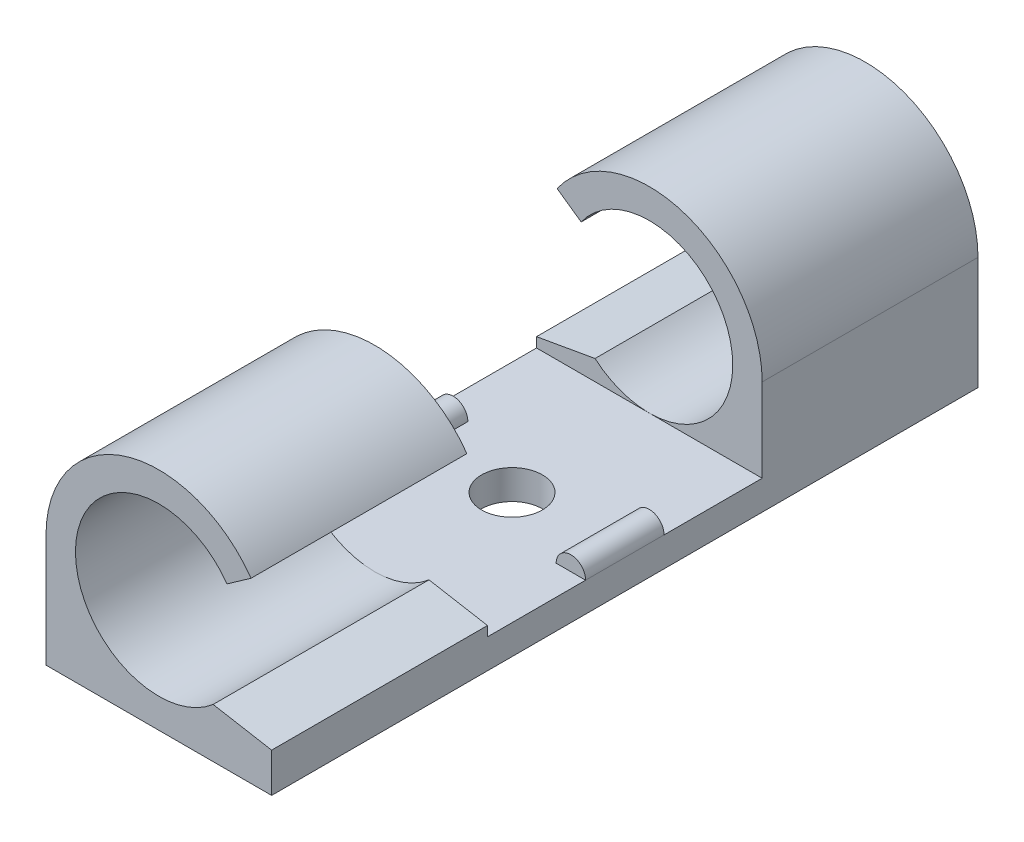
SolidWorks part; units mm, degrees
ref_plane "Plano frontal" through (0, 0, 0) normal (0, 0, 1) x (1, 0, 0)
ref_plane "Plano superior" through (0, 0, 0) normal (0, 1, 0) x (1, 0, 0)
ref_plane "Plano direito" through (0, 0, 0) normal (1, 0, 0) x (0, 0, -1)
sketch "Esboço1" plane through (0, 0, 0) normal (0, 0, 1) x (1, 0, 0)
  line L0 (-5.75, 0) -> (5.75, 0)
  line L1 (-5.75, 5.75) -> (5.75, 5.75)
  line L2 (-5.75, 5.75) -> (-5.75, -5.75)
  line L3 (-5.75, -5.75) -> (5.75, -5.75)
  line L4 (5.75, 5.75) -> (5.75, -5.75)
  line L5 (-5.75, 5.75) -> (5.75, -5.75) construction
  line L6 (-5.75, -5.75) -> (5.75, 5.75) construction
  circle A0 centre (0, 0) radius 5.75
  circle A2 centre (0, 0) radius 4.25
  point P0 (0, 0)
  point P12 (0, 0)
  dimension "D3" = 8.5
  dimension "D1" = 11.5
  dimension "D2" = 11.5
extrude "Ressalto-extrusão1" add sketch "Esboço1" along normal blind 11 contours A0 L2 L3 | A0 L3 L4 | A2 L0 A0 | A2 L0 A0 region at (0, 4.3786, 0) region at (5, -0.1286, 0) region at (4.4656, -4.4656, 0) region at (-4.4656, -4.4656, 0)
sketch "Esboço2" plane through (0, 0, 11) normal (0, 0, 1) x (1, 0, 0)
  line L0 (5.75, 0) -> (5.75, -5.75) construction
  line L1 (-5.75, -5.75) -> (5.75, -5.75)
  line L2 (-5.75, -5.75) -> (-5.75, -4.25)
  line L3 (-5.75, -4.25) -> (5.75, -4.25)
  line L4 (5.75, -5.75) -> (5.75, -4.25)
  line L5 (-5.75, -5.75) -> (5.75, -4.25) construction
  line L6 (-5.75, -4.25) -> (5.75, -5.75) construction
  circle A0 centre (0, 0) radius 4.25 construction
  point P4 (0, -5)
extrude "Ressalto-extrusão2" add sketch "Esboço2" along normal blind 7
sketch "Esboço3" plane through (0, 0, 18) normal (0, 0, 1) x (1, 0, 0)
  line L0 (5.75, -4.25) -> (0, -4.25) construction
  line L1 (5.75, -4.25) -> (0, -4.25) construction
  line L2 (0, 0) -> (0, -0.723) construction
  arc A0 (5.75, -4.25) -> (4.25, -4.25) centre (5, -4.25) ccw
  arc A1 (4.25, -4.25) -> (5.75, -4.25) centre (5, -4.25) ccw construction
  arc A2 (-5.75, -4.25) -> (-4.25, -4.25) centre (-5, -4.25) cw
  line M5 (5.75, -4.25) -> (-5.75, -4.25)
  dimension "D1" = 1.5
extrude "Ressalto-extrusão3" add sketch "Esboço3" against normal blind 2 contours A0 M5 | A2 M5 region at (5, -3.9317, 18) region at (-5, -3.9317, 18)
mirror "Espelhar1" about plane through (0, 0, 18) normal (0, 0, -1) of "Ressalto-extrusão2", "Ressalto-extrusão1", "Ressalto-extrusão3"
sketch "Esboço4" plane through (0, -4.25, 0) normal (0, 1, 0) x (1, 0, 0)
  line L0 (0, -11) -> (0, -18) construction
  line L2 (-4.25, -18) -> (4.25, -18) construction
  line L3 (-4.25, -16) -> (-4.25, -20) construction
  line L4 (4.25, -16) -> (4.25, -20) construction
  line L5 (-5.75, -11) -> (5.75, -11) construction
  circle A0 centre (0, -18) radius 1.55
  point P2 (0, 0)
  point P13 (0, -17.7766)
  dimension "D1" = 3.1
extrude "Corte-extrusão1" cut sketch "Esboço4" against normal blind 2
sketch "Esboço5" plane through (0, 0, 36) normal (0, 0, 1) x (1, 0, 0)
  line L0 (5.75, -3.75) -> (2, -3.75) construction
  line L1 (5.75, 0) -> (5.75, -5.75) construction
  line L2 (-5.75, -5.75) -> (5.75, -5.75) construction
  line L3 (5.2915, 2.25) -> (3.1939, 2.25) construction
  line L4 (3.1939, 2.25) -> (4.7007, 3.3115)
  line L5 (0, 0) -> (3.1939, 2.25) construction
  line L6 (5.75, -3.75) -> (2.7688, -3.2243)
  circle A0 centre (0, 0) radius 4.25 construction
  arc A1 (5.75, 0) -> (-5.75, 0) centre (0, 0) ccw construction
  circle M4 centre (0, 0) radius 4.25
  line M6 (5.75, -5.75) -> (5.75, 0)
  arc M7 (5.75, 0) -> (-5.75, 0) centre (0, 0) ccw
  dimension "D1" = 2
  dimension "D2" = 6
  dimension "D3" = 35.164
  dimension "D4" = 10
extrude "Corte-extrusão2" cut sketch "Esboço5" against normal blind 12 contours L4 L0 M4 M6 M7 region at (4.729, -0.6115, 36)
sketch "Esboço6" plane through (0, 0, 0) normal (0, 0, -1) x (-1, 0, 0)
  line L0 (5.75, -3.75) -> (2, -3.75) construction
  line L1 (5.75, 0) -> (5.75, -5.75) construction
  line L2 (5.75, -5.75) -> (-5.75, -5.75) construction
  line L3 (5.2031, 2.4474) -> (3.4746, 2.4474) construction
  line L4 (5.75, -3.75) -> (2.7688, -3.2243)
  line L5 (3.4746, 2.4474) -> (5.4041, 3.8065)
  line L6 (0, 0) -> (3.4746, 2.4474) construction
  circle A0 centre (0, 0) radius 4.25 construction
  arc A1 (5.75, 0) -> (-5.75, 0) centre (0, 0) ccw construction
  circle M3 centre (0, 0) radius 4.25
  line M5 (5.75, -5.75) -> (5.75, 0)
  arc M6 (5.75, 0) -> (-5.75, 0) centre (0, 0) ccw
  dimension "D1" = 2
  dimension "D2" = 35.16
  dimension "D3" = 10
extrude "Corte-extrusão3" cut sketch "Esboço6" against normal blind 12 contours L5 L4 M3 M5 M6 region at (-4.729, -0.6117, 0)
equation "\"D2@Esboço1\"=\"D1@Esboço1\""
equation "\"D1@Esboço1\"=\"D3@Esboço1\"+3"
